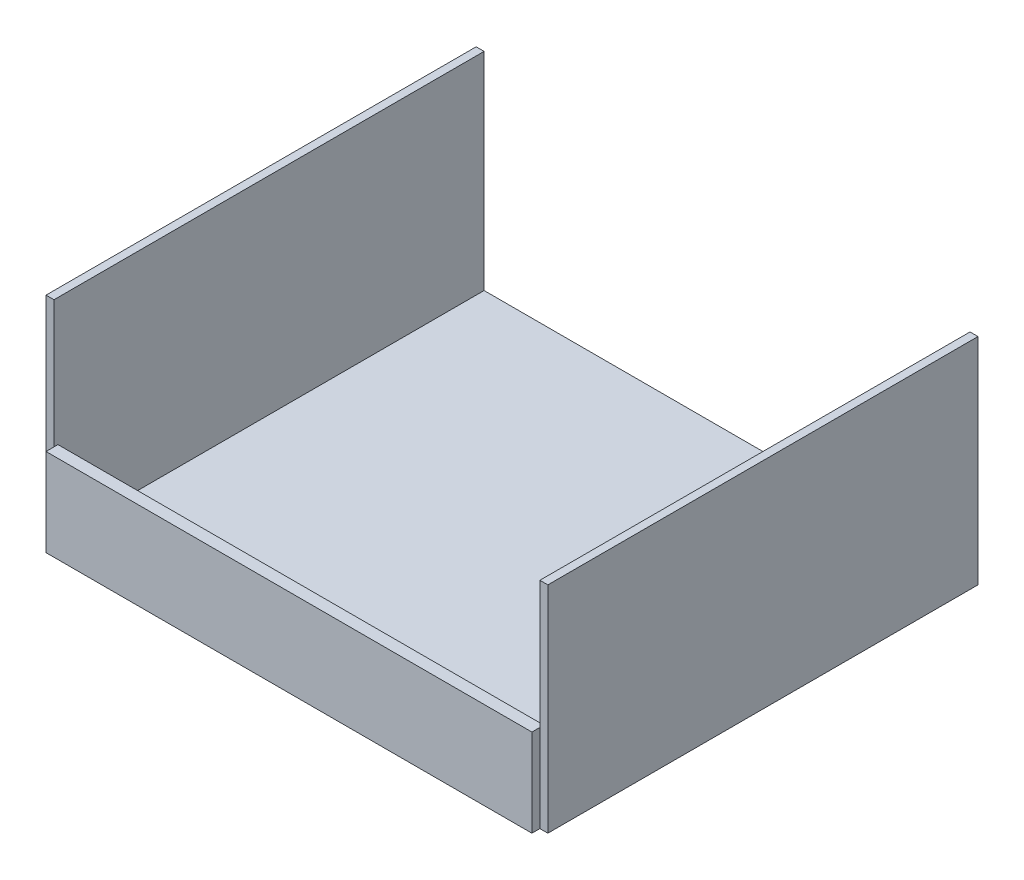
SolidWorks part; units mm, degrees
ref_plane "Front Plane" through (0, 0, 0) normal (0, 0, 1) x (1, 0, 0)
ref_plane "Top Plane" through (0, 0, 0) normal (0, 1, 0) x (1, 0, 0)
ref_plane "Right Plane" through (0, 0, 0) normal (1, 0, 0) x (0, 0, -1)
sketch "Sketch2" plane through (0, 0, 0) normal (0, 1, 0) x (1, 0, 0)
  line L1 (-111.3245, 129.7328) -> (88.7005, 129.7328)
  line L2 (-111.3245, 129.7328) -> (-111.3245, -41.7172)
  line L3 (-111.3245, -41.7172) -> (88.7005, -41.7172)
  line L4 (88.7005, 129.7328) -> (88.7005, -41.7172)
  dimension "D1" = 171.45
  dimension "D2" = 200.025
extrude "Boss-Extrude1" add sketch "Sketch2" along normal blind 3.175
sketch "Sketch3" plane through (0, 3.175, 0) normal (0, 1, 0) x (1, 0, 0)
  line L0 (-111.3245, -41.7172) -> (88.7005, -41.7172) construction
  line L1 (-111.3245, 129.7328) -> (-108.1495, 129.7328)
  line L2 (-111.3245, 129.7328) -> (-111.3245, -41.7172)
  line L3 (-111.3245, -41.7172) -> (-108.1495, -41.7172)
  line L4 (-108.1495, 129.7328) -> (-108.1495, -41.7172)
  line L6 (88.7005, 129.7328) -> (85.5255, 129.7328)
  line L7 (88.7005, 129.7328) -> (88.7005, -41.7172)
  line L8 (88.7005, -41.7172) -> (85.5255, -41.7172)
  line L9 (85.5255, 129.7328) -> (85.5255, -41.7172)
  dimension "D1" = 3.175
  dimension "D2" = 3.175
extrude "Boss-Extrude2" add sketch "Sketch3" along normal blind 82.55
sketch "Sketch6" plane through (0, 0, 0) normal (0, -1, 0) x (1, 0, 0)
  line L5 (-111.3245, 41.7172) -> (88.7005, 41.7172) construction
  line L6 (-108.1495, 23.268) -> (85.5255, 23.268)
  line L7 (-108.1495, 23.268) -> (-108.1495, 44.8922)
  line L8 (-108.1495, 44.8922) -> (85.5255, 44.8922)
  line L9 (85.5255, 23.268) -> (85.5255, 44.8922)
  dimension "D1" = 3.175
extrude "Boss-Extrude13" add sketch "Sketch6" against normal blind 3.175 contours L8 L9 L6 L7
sketch "Sketch7" plane through (0, 3.175, 0) normal (0, 1, 0) x (1, 0, 0)
  line L0 (85.5255, 129.7328) -> (85.5255, -41.7172) construction
  line L5 (-108.1495, -44.8922) -> (85.5255, -44.8922)
  line L6 (-108.1495, -44.8922) -> (-108.1495, -40.1297)
  line L7 (-108.1495, -40.1297) -> (85.5255, -40.1297)
  line L8 (85.5255, -44.8922) -> (85.5255, -40.1297)
  dimension "D1" = 4.7625
extrude "Boss-Extrude23" add sketch "Sketch7" along normal blind 31.75 contours L5 L8 L7 L6
